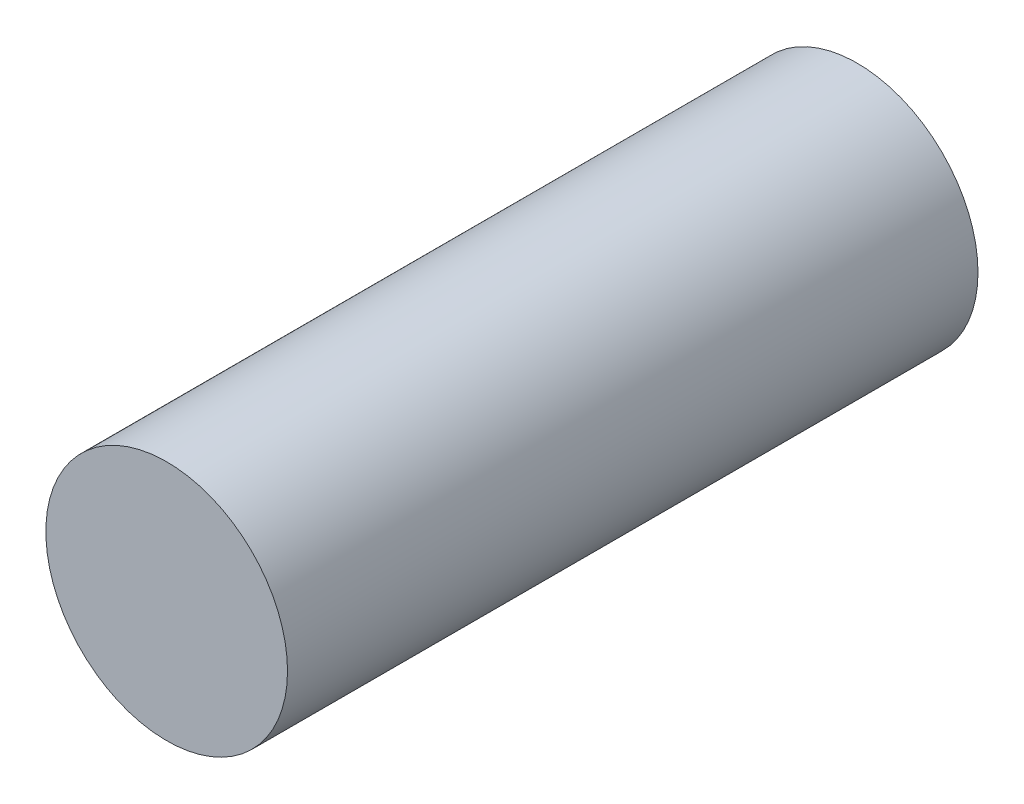
SolidWorks part; units mm, degrees
ref_plane "Front Plane" through (0, 0, 0) normal (0, 0, 1) x (1, 0, 0)
ref_plane "Top Plane" through (0, 0, 0) normal (0, 1, 0) x (1, 0, 0)
ref_plane "Right Plane" through (0, 0, 0) normal (1, 0, 0) x (0, 0, -1)
sketch "Sketch1" plane through (0, 0, 0) normal (0, 0, 1) x (1, 0, 0)
  circle A0 centre (0, 0) radius 3.1115
  dimension "D1" = 6.223
extrude "Boss-Extrude1" add sketch "Sketch1" along normal blind 17.78
